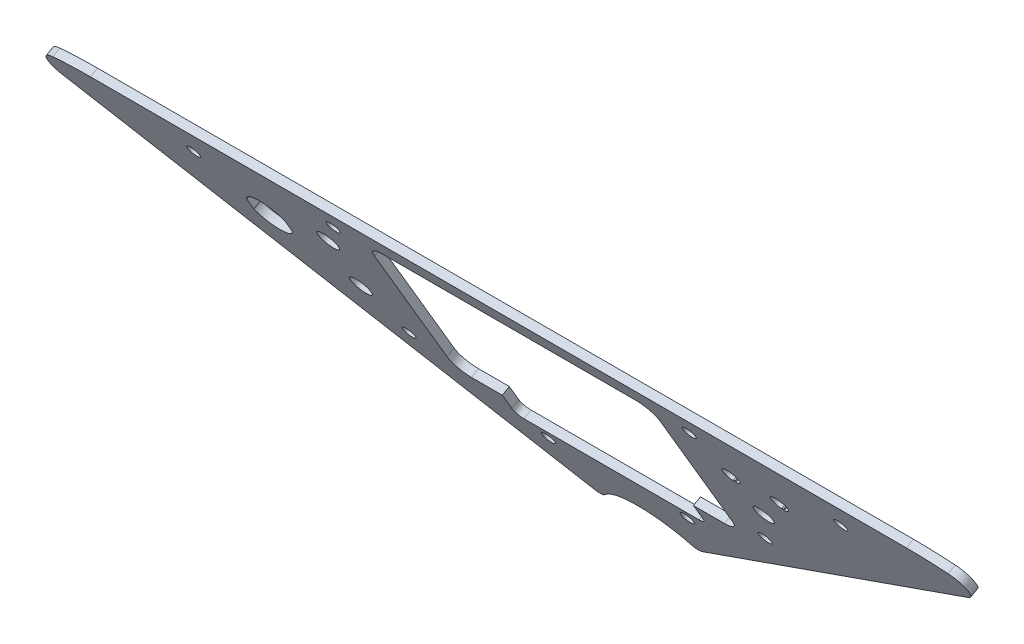
SolidWorks part; units mm, degrees
material "Thornel VCB-20 Carbon Cloth"
ref_plane "Front Plane" through (0, 0, 0) normal (0, 0, 1) x (1, 0, 0)
ref_plane "Top Plane" through (0, 0, 0) normal (0, 1, 0) x (1, 0, 0)
ref_plane "Right Plane" through (0, 0, 0) normal (1, 0, 0) x (0, 0, -1)
ref_plane "Plane1" through (0, -119.0262, 202.5184) normal (0, 0.5067, -0.8621) x (-1, 0, 0)
ref_axis "Axis1" through (-138.1707, 616.7078, 646.8636) along (0.8355, -0.4738, -0.2785)
sketch "Sketch2" plane through (0, -119.0262, 202.5184) normal (0, 0.5067, -0.8621) x (-1, 0, 0)
  line L0 (21.0542, 782.405) -> (177.8755, 885.5596)
  line L1 (138.1707, 859.4424) -> (70.4504, 814.8971) construction
  line L2 (0, 1972.2008) -> (0, -1972.2008) construction
  line L5 (0, 898.6914) -> (0, 768.5559) construction
  line L7 (160.0992, 922.5039) -> (160.0992, 897.1039) construction
  line L9 (160.0992, 898.6914) -> (-160.0992, 898.6914)
  line L10 (-160.0992, 897.1039) -> (160.0992, 897.1039) construction
  line L11 (-21.0542, 782.405) -> (-177.8755, 885.5596)
  arc A0 (16.8957, 782.9949) -> (-16.8957, 782.9949) centre (0, 768.5559) ccw
  circle A3 centre (-127, 884.165) radius 2.4892
  circle A4 centre (-27.2422, 806.1914) radius 2.4892
  circle A5 centre (27.2422, 806.1914) radius 2.4892
  circle A6 centre (127, 884.165) radius 2.4892
  arc A7 (160.0992, 898.6914) -> (175.6846, 897.0805) centre (160.0992, 822.4914) cw
  arc A8 (175.6846, 897.0805) -> (177.8755, 885.5596) centre (174.3858, 890.8648) cw
  arc A9 (-160.0992, 898.6914) -> (-175.6846, 897.0805) centre (-160.0992, 822.4914) ccw
  arc A10 (-175.6846, 897.0805) -> (-177.8755, 885.5596) centre (-174.3858, 890.8648) ccw
  arc A11 (21.0542, 782.405) -> (16.8957, 782.9949) centre (19.3094, 785.0576) cw
  arc A12 (-21.0542, 782.405) -> (-16.8957, 782.9949) centre (-19.3094, 785.0576) ccw
  point P37 (18.5681, 780.7697)
  point P40 (-18.5681, 780.7697)
  dimension "D1" = 22.225
  dimension "D2" = 1.5875
  dimension "D3" = 6.35
  dimension "D4" = 4.9784
  dimension "D5" = 76.2
  dimension "D6" = 3.175
extrude "Boss-Extrude1" add sketch "Sketch2" along normal blind 3.175
sketch "Sketch4" plane through (0, -117.4174, 199.7812) normal (0, 0.5067, -0.8621) x (-1, 0, 0)
  circle A0 centre (-69.85, 888.7539) radius 2.4892
  circle A1 centre (-69.85, 830.0164) radius 2.4892
  circle A2 centre (69.85, 830.0164) radius 2.4892
  circle A3 centre (69.85, 888.7539) radius 2.4892
  dimension "D1" = 4.9784
extrude "Cut-Extrude1" cut sketch "Sketch4" against normal through all
sketch "Sketch6" plane through (0, -119.0262, 202.5184) normal (0, -0.5067, 0.8621) x (1, 0, 0)
  circle A0 centre (-79.654, 873.2914) radius 4
  circle A1 centre (-79.654, 847.8914) radius 4
  dimension "D1" = 8
extrude "Cut-Extrude3" cut sketch "Sketch6" against normal through all
sketch "Sketch5" plane through (0, -117.4174, 199.7812) normal (0, 0.5067, -0.8621) x (-1, 0, 0)
  line L1 (21.0542, 782.405) -> (177.8755, 885.5596) construction
  line L2 (99.2157, 862.57) -> (99.2157, 868.1378)
  line L3 (114.2157, 868.1378) -> (114.2157, 862.57)
  line L5 (160.0992, 898.6914) -> (-160.0992, 898.6914) construction
  arc A0 (99.2157, 862.57) -> (114.2157, 862.57) centre (106.7157, 865.3539) ccw
  arc A1 (114.2157, 868.1378) -> (99.2157, 868.1378) centre (106.7157, 865.3539) ccw
  point P3 (79.654, 873.2914)
  dimension "D1" = 16
  dimension "D3" = 22.225
  dimension "D2" = 33.3375
  dimension "D4" = 15
extrude "Cut-Extrude2" cut sketch "Sketch5" against normal through all
sketch "Sketch7" plane through (0, -117.4174, 199.7812) normal (0, 0.5067, -0.8621) x (-1, 0, 0)
  line L0 (-69.85, 888.7539) -> (-69.85, 830.0164) construction
  line L1 (-80.925, 863.9977) -> (-73.025, 863.9977) construction
  line L2 (-80.925, 863.9977) -> (-80.925, 876.9977) construction
  line L3 (-80.925, 876.9977) -> (-73.025, 876.9977) construction
  line L4 (-73.025, 863.9977) -> (-73.025, 876.9977) construction
  line L5 (-80.925, 863.9977) -> (-73.025, 876.9977) construction
  line L6 (-80.925, 876.9977) -> (-73.025, 863.9977) construction
  line L7 (-92.075, 863.9977) -> (-99.975, 863.9977) construction
  line L8 (-92.075, 863.9977) -> (-92.075, 876.9977) construction
  line L9 (-92.075, 876.9977) -> (-99.975, 876.9977) construction
  line L10 (-99.975, 863.9977) -> (-99.975, 876.9977) construction
  line L11 (-92.075, 863.9977) -> (-99.975, 876.9977) construction
  line L12 (-92.075, 876.9977) -> (-99.975, 863.9977) construction
  line L13 (-96.025, 870.4977) -> (-80.15, 851.4477) construction
  line L15 (-77.2798, 867.2608) -> (-77.2798, 867.9577)
  line L16 (-77.2798, 867.9577) -> (-76.6702, 867.9577)
  line L17 (-76.6702, 867.2608) -> (-76.6702, 867.9577)
  line L19 (-96.3298, 867.2608) -> (-96.3298, 867.9577)
  line L20 (-96.3298, 867.9577) -> (-95.7202, 867.9577)
  line L21 (-95.7202, 867.2608) -> (-95.7202, 867.9577)
  line L22 (-80.15, 851.4477) -> (-76.975, 870.4977) construction
  line L24 (-73.45, 845.1977) -> (-86.85, 845.1977) construction
  line L25 (-73.45, 845.1977) -> (-73.45, 857.6977) construction
  line L26 (-73.45, 857.6977) -> (-86.85, 857.6977) construction
  line L27 (-86.85, 845.1977) -> (-86.85, 857.6977) construction
  line L28 (-73.45, 845.1977) -> (-86.85, 857.6977) construction
  line L29 (-73.45, 857.6977) -> (-86.85, 845.1977) construction
  circle A0 centre (-69.85, 888.7539) radius 2.4892 construction
  arc A1 (-76.6702, 867.2608) -> (-77.2798, 867.2608) centre (-76.975, 870.4977) ccw
  arc A2 (-95.7202, 867.2608) -> (-96.3298, 867.2608) centre (-96.025, 870.4977) ccw
  circle A3 centre (-80.15, 851.4477) radius 3.75
  point P0 (-76.975, 870.4977)
  point P5 (-96.025, 870.4977)
  point P10 (-69.85, 859.3852)
  dimension "D5" = 6.5024
  dimension "D9" = 7.5
  dimension "D1" = 13
  dimension "D2" = 7.9
  dimension "D3" = 19.05
  dimension "D4" = 3.175
  dimension "D6" = 11.1125
  dimension "D7" = 0.6096
  dimension "D8" = 5.7912
  dimension "D10" = 12.5
  dimension "D11" = 13.4
  dimension "D12" = 19.05
  dimension "D13" = 3.175
extrude "Cut-Extrude4" cut sketch "Sketch7" against normal through all
sketch "Sketch8" plane through (0, -117.4174, 199.7812) normal (0, 0.5067, -0.8621) x (-1, 0, 0)
  line L1 (49.65, 890.4289) -> (-49.65, 890.4289)
  line L2 (56, 884.0789) -> (56, 827.9789)
  line L3 (49.65, 821.6289) -> (37.5, 821.6289)
  line L4 (-56, 884.0789) -> (-56, 827.9789)
  line L5 (56, 890.4289) -> (-56, 821.6289) construction
  line L6 (56, 821.6289) -> (-56, 890.4289) construction
  line L7 (-54.4125, 888.8414) -> (-54.4125, 823.2164) construction
  line L8 (54.4125, 823.2164) -> (54.4125, 888.8414) construction
  line L9 (-54.4125, 823.2164) -> (54.4125, 823.2164) construction
  line L10 (54.4125, 888.8414) -> (-54.4125, 888.8414) construction
  line L11 (-37.5, 814.2874) -> (-37.5, 821.6289)
  line L12 (-37.5, 811.1124) -> (-37.5, 815.8749) construction
  line L13 (37.5, 821.6289) -> (37.5, 814.2874)
  line L14 (34.325, 811.1124) -> (-34.325, 811.1124)
  line L15 (-37.5, 821.6289) -> (-49.65, 821.6289)
  arc A0 (-49.65, 821.6289) -> (-56, 827.9789) centre (-49.65, 827.9789) cw
  arc A1 (56, 827.9789) -> (49.65, 821.6289) centre (49.65, 827.9789) cw
  arc A2 (49.65, 890.4289) -> (56, 884.0789) centre (49.65, 884.0789) cw
  arc A3 (-49.65, 890.4289) -> (-56, 884.0789) centre (-49.65, 884.0789) ccw
  arc A4 (37.5, 814.2874) -> (34.325, 811.1124) centre (34.325, 814.2874) cw
  arc A5 (-37.5, 814.2874) -> (-34.325, 811.1124) centre (-34.325, 814.2874) ccw
  point P0 (0, 856.0289)
  point P34 (37.5, 811.1124)
  point P37 (-37.5, 811.1124)
  dimension "D5" = 6.35
  dimension "D6" = 3.175
  dimension "D1" = 1.5875
  dimension "D2" = 1.5875
  dimension "D3" = 1.5875
  dimension "D4" = 1.5875
extrude "Cut-Extrude5" cut sketch "Sketch8" against normal through all
